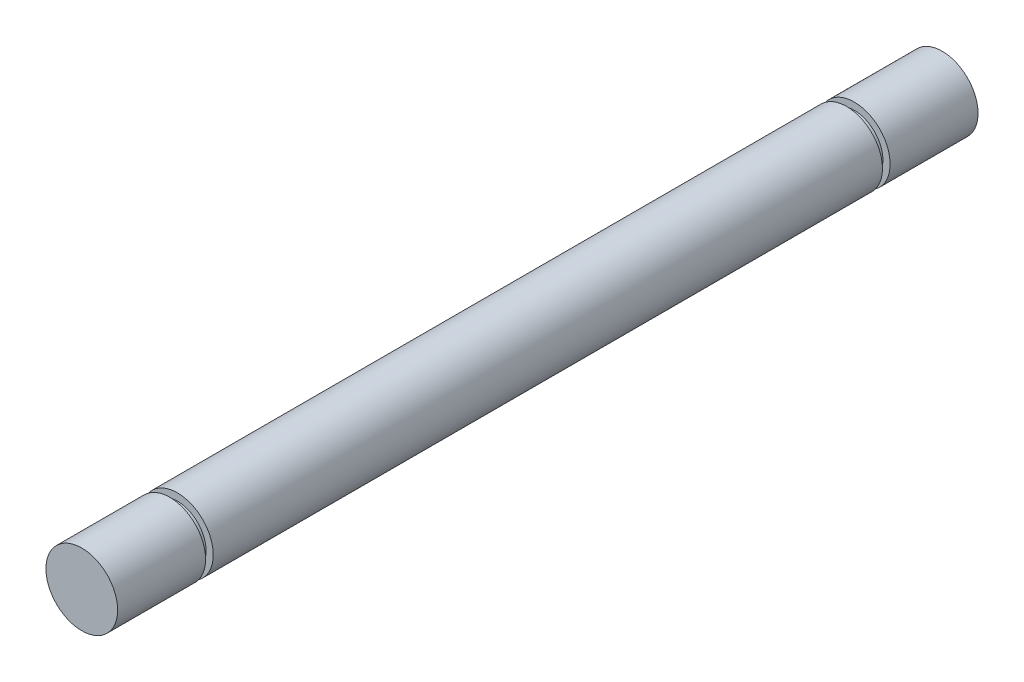
SolidWorks part; units mm, degrees
ref_plane "Front Plane" through (0, 0, 0) normal (0, 0, 1) x (1, 0, 0)
ref_plane "Top Plane" through (0, 0, 0) normal (0, 1, 0) x (1, 0, 0)
ref_plane "Right Plane" through (0, 0, 0) normal (1, 0, 0) x (0, 0, -1)
sketch "Sketch1" plane through (0, 0, 0) normal (0, 0, 1) x (1, 0, 0)
  circle A0 centre (0, 0) radius 4.7625
  dimension "D1" = 9.525
extrude "Boss-Extrude1" add sketch "Sketch1" along normal blind 88.9
sketch "Sketch2" plane through (0, 0, 0) normal (0, 0, -1) x (-1, 0, 0)
  circle A0 centre (0, 0) radius 3.81
  dimension "D1" = 7.62
extrude "Boss-Extrude2" add sketch "Sketch2" along normal blind 1.016
sketch "Sketch3" plane through (0, 0, -1.016) normal (0, 0, -1) x (-1, 0, 0)
  circle A0 centre (0, 0) radius 4.7625
  dimension "D1" = 9.525
extrude "Boss-Extrude3" add sketch "Sketch3" along normal blind 11.684
sketch "Sketch4" plane through (0, 0, 88.9) normal (0, 0, 1) x (1, 0, 0)
  circle A0 centre (0, 0) radius 3.81
  dimension "D1" = 7.62
extrude "Boss-Extrude4" add sketch "Sketch4" along normal blind 1.016
sketch "Sketch5" plane through (0, 0, 89.916) normal (0, 0, 1) x (1, 0, 0)
  circle A0 centre (0, 0) radius 4.7625
  dimension "D1" = 9.525
extrude "Boss-Extrude5" add sketch "Sketch5" along normal blind 11.684
